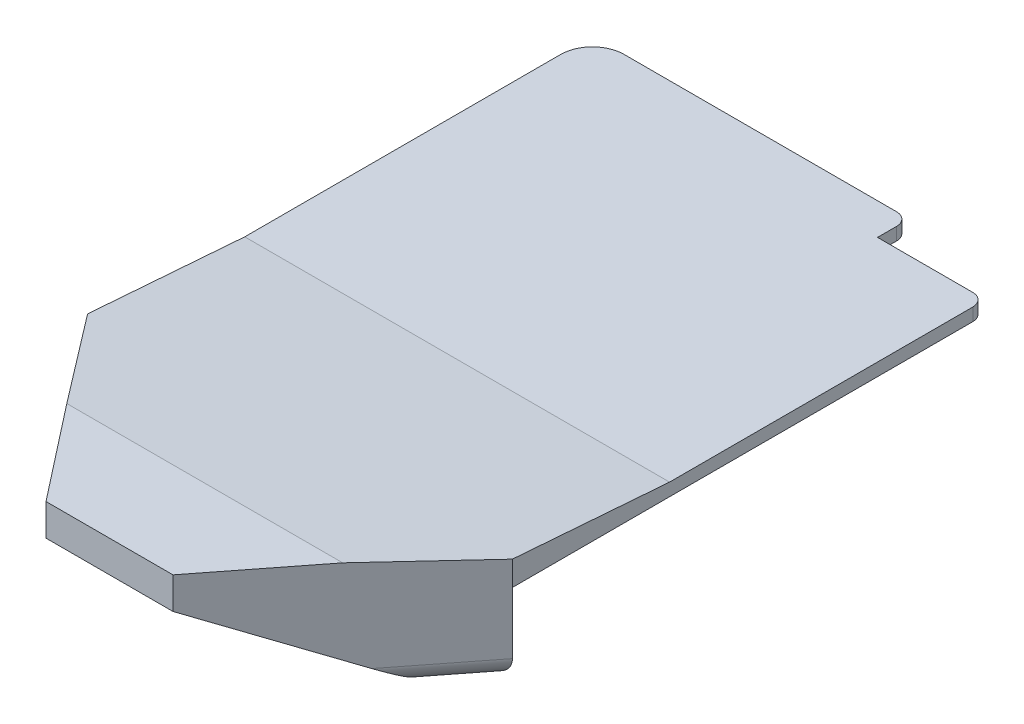
SolidWorks part; units mm, degrees
ref_plane "Front Plane" through (0, 0, 0) normal (0, 0, 1) x (1, 0, 0)
ref_plane "Top Plane" through (0, 0, 0) normal (0, 1, 0) x (1, 0, 0)
ref_plane "Right Plane" through (0, 0, 0) normal (1, 0, 0) x (0, 0, -1)
sketch "Sketch1" plane through (0, 0, 0) normal (0, 1, 0) x (1, 0, 0)
  line L0 (0, 0) -> (-16.35, 0)
  line L1 (-16.35, 0) -> (-16.35, -9.85)
  line L2 (-16.35, -9.85) -> (-2.6, -9.85)
  line L3 (-20.1, -33) -> (-20.1, -75)
  line L4 (-20.1, -75) -> (0, -75)
  line L5 (0, -75) -> (0, 0)
  line L6 (-2.6, -9.85) -> (-2.6, -33)
  line L7 (-2.6, -33) -> (-20.1, -33)
  dimension "D1" = 16.35
  dimension "D2" = 9.85
  dimension "D3" = 13.75
  dimension "D4" = 3.75
  dimension "D5" = 23.15
  dimension "D6" = 42
extrude "Boss-Extrude1" add sketch "Sketch1" along normal blind 7.7
sketch "Sketch2" plane through (0, 0, 75) normal (0, 0, 1) x (1, 0, 0)
  line L0 (-20.1, 7.7) -> (-20.1, 0) construction
  line L1 (-20.1, 5.1) -> (-13.1, 5.1)
  line L2 (-20.1, 5.1) -> (-20.1, 2)
  line L3 (-20.1, 2) -> (-13.1, 2)
  line L4 (-13.1, 5.1) -> (-13.1, 2)
  line L5 (-20.1, 0) -> (0, 0) construction
  dimension "D1" = 7
  dimension "D2" = 3.1
  dimension "D3" = 2
extrude "Cut-Extrude1" cut sketch "Sketch2" against normal through all
fillet "Fillet1" radius 10 1 edges at (-2.6, 3.85, 33)
sketch "Sketch3" plane through (0, 7.7, 0) normal (0, 1, 0) x (1, 0, 0)
  line L0 (0, 0) -> (0, -75)
  line L1 (0, -75) -> (-33.45, -75)
  line L2 (-33.45, -75) -> (-33.45, 0)
  line L3 (-33.45, 0) -> (0, 0)
  line L4 (0, -75) -> (0, -105)
  line L5 (0, -105) -> (-10, -105)
  line L6 (0, 0) -> (0, 4.5)
  line L7 (-33.45, -75) -> (-10, -105)
  line L8 (0, 4.5) -> (-33.45, 4.5)
  line L9 (-33.45, 4.5) -> (-33.45, 0)
  dimension "D1" = 33.45
  dimension "D2" = 30
  dimension "D3" = 10
  dimension "D4" = 4.5
extrude "Boss-Extrude2" add sketch "Sketch3" along normal blind 2
sketch "Sketch4" plane through (0, 0, 0) normal (1, 0, 0) x (0, 0, -1)
  line L0 (-105, 9.7) -> (-105, 12.7)
  line L1 (-105, 12.7) -> (-90, 12.7)
  line L2 (-90, 12.7) -> (-50.25, 9.7)
  line L3 (-105, 9.7) -> (4.5, 9.7) construction
  line L4 (-105, 9.7) -> (-50.25, 9.7)
  point P8 (-50.25, 9.7)
  dimension "D1" = 15
  dimension "D2" = 3
extrude "Boss-Extrude3" add sketch "Sketch4" against normal up to surface (33.45 mm away) up to face at (-33.45, 8.7, 35.25)
sketch "Sketch5" plane through (-33.45, 0, 0) normal (-1, 0, 0) x (0, 0, 1)
  line L0 (75, 7.7) -> (75, -5)
  line L1 (75, -5) -> (82, -5)
  line L2 (82, -5) -> (105, 7.7)
  line L3 (105, 7.7) -> (75, 7.7)
  line L4 (33, 0) -> (75, 0) construction
  dimension "D1" = 5
  dimension "D2" = 7
extrude "Boss-Extrude4" add sketch "Sketch5" against normal up to surface (33.45 mm away) up to face at (0, 7.56, 49.125)
sketch "Sketch6" plane through (0, 7.7, 0) normal (0, 1, 0) x (1, 0, 0)
  line L0 (-33.45, -75) -> (-10, -105)
  line L1 (-10, -105) -> (-33.45, -105)
  line L2 (-33.45, -105) -> (-33.45, -75)
extrude "Cut-Extrude2" cut sketch "Sketch6" against normal through all both and the other way through all
sketch "Sketch7" plane through (0, 0, 0) normal (1, 0, 0) x (0, 0, -1)
  line L0 (-75, 0) -> (-85, 0)
  line L1 (-85, 0) -> (-80, -5)
  line L2 (-82, -5) -> (-75, -5) construction
  line L3 (-80, -5) -> (-75, -5)
  line L4 (-75, -5) -> (-75, 0)
  dimension "D1" = 5
  dimension "D2" = 10
extrude "Cut-Extrude3" cut sketch "Sketch7" against normal blind 10
fillet "Fillet3" radius 1 2 edges at (-5, -5, 80) (-10, -5, 77.5)
fillet "Fillet4" [suppressed] radius 5
mirror "Mirror1" about plane through (0, 7.7, 75) normal (-1, 0, 0) of bodies 110
fillet "Fillet5" radius 3 2 edges at (-30.7142, -5, 78.5) (30.7142, -5, 78.5)
sketch "Sketch8" plane through (0, 9.7, 0) normal (0, 1, 0) x (1, 0, 0)
  line L0 (33.45, 4.5) -> (33.45, -0.5)
  line L1 (33.45, -50.25) -> (33.45, 4.5) construction
  line L2 (33.45, -0.5) -> (16.45, -0.5)
  line L3 (16.45, -0.5) -> (16.45, 4.5)
  line L4 (33.45, 4.5) -> (-33.45, 4.5) construction
  line L5 (16.45, 4.5) -> (33.45, 4.5)
  dimension "D1" = 5
  dimension "D2" = 17
extrude "Cut-Extrude4" cut sketch "Sketch8" against normal blind 2
fillet "Fillet6" radius 5 1 edges at (-33.45, 8.7, -4.5)
fillet "Fillet7" radius 2 2 edges at (33.45, 8.7, 0.5) (16.45, 8.7, -4.5)
